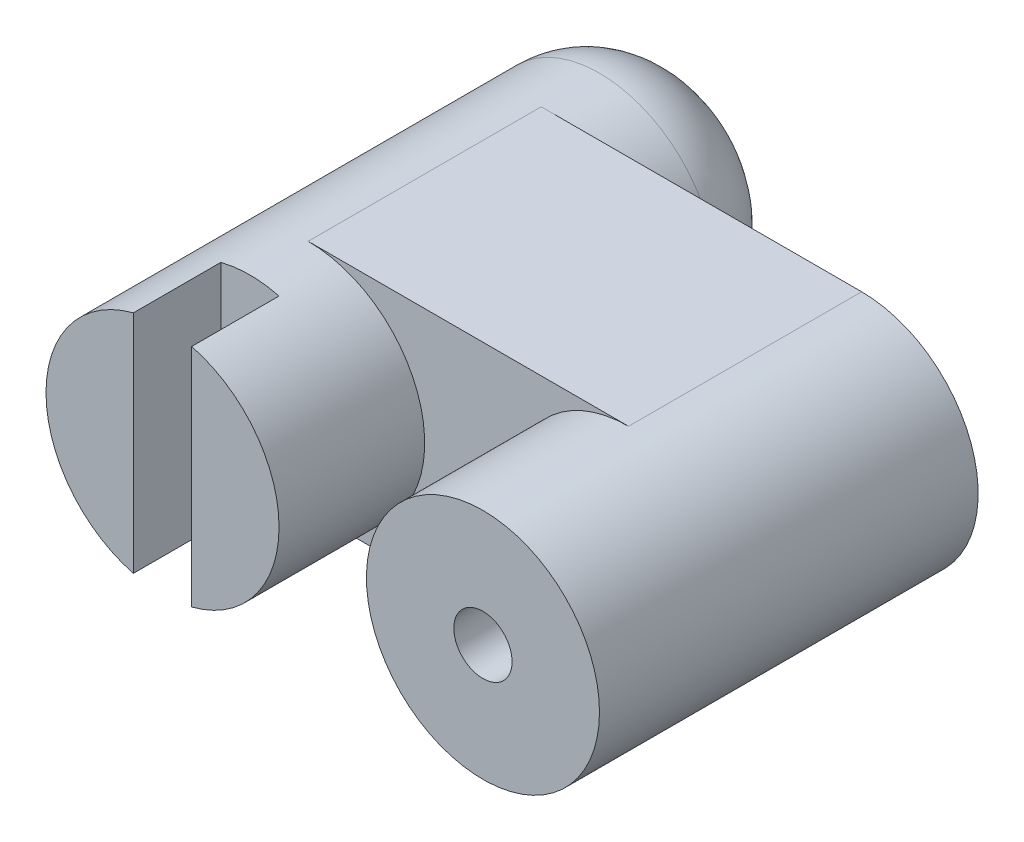
SolidWorks part; units mm, degrees
ref_plane "前视基准面" through (0, 0, 0) normal (0, 0, 1) x (1, 0, 0)
ref_plane "上视基准面" through (0, 0, 0) normal (0, 1, 0) x (1, 0, 0)
ref_plane "右视基准面" through (0, 0, 0) normal (1, 0, 0) x (0, 0, -1)
other "Configuration Table"
sketch "草图1" plane through (0, 0, 0) normal (0, 0, 1) x (1, 0, 0)
  circle A0 centre (0, 0) radius 2
  circle A1 centre (0, 0) radius 0.5
  dimension "D1" = 4
  dimension "D2" = 1
extrude "凸台-拉伸1" add sketch "草图1" along normal blind 9
sketch "草图2" plane through (0, 0, 9) normal (0, 0, 1) x (1, 0, 0)
  line L1 (-0.5, -2.0824) -> (0.5, -2.0824)
  line L2 (-0.5, -2.0824) -> (-0.5, 2.0824)
  line L3 (-0.5, 2.0824) -> (0.5, 2.0824)
  line L4 (0.5, -2.0824) -> (0.5, 2.0824)
  line L5 (-0.5, -2.0824) -> (0.5, 2.0824) construction
  line L6 (-0.5, 2.0824) -> (0.5, -2.0824) construction
  point P0 (0, 0)
  dimension "D1" = 1
extrude "切除-拉伸1" cut sketch "草图2" against normal blind 1.5
fillet "圆角2" radius 1.5 1 edges at (2, 0, 0)
sketch "草图3" plane through (0, 0, 0) normal (0, 1, 0) x (1, 0, 0)
  line L0 (0, 0) -> (0, -2.5) construction
  line L1 (0, -2.5) -> (0, -6.5)
  line L2 (0, -2.5) -> (5.5, -2.5)
  line L3 (5.5, -2.5) -> (5.5, -6.5)
  line L4 (0, -6.5) -> (5.5, -6.5)
  dimension "D1" = 2.5
  dimension "D2" = 4
  dimension "D3" = 5.5
  dimension "D4" = 4
extrude "凸台-拉伸2" add sketch "草图3" along normal mid plane 4
sketch "草图4" plane through (0, 0, 2.5) normal (0, 0, -1) x (-1, 0, 0)
  line L0 (-5.5, 2) -> (-5.5, -2) construction
  circle A0 centre (-5.5, 0) radius 2
  circle A1 centre (-5.5, 0) radius 0.5
  dimension "D1" = 1
extrude "凸台-拉伸3" add sketch "草图4" against normal blind 4
sketch "草图5" plane through (0, 0, 2.5) normal (0, 0, -1) x (-1, 0, 0)
  line L0 (-5.5, 0.5) -> (-5.5, -0.5) construction
  circle A0 centre (-5.5, 0) radius 0.5
  dimension "D1" = 1
extrude "切除-拉伸2" cut sketch "草图5" against normal blind 4
sketch "草图6" plane through (0, 0, 9) normal (0, 0, 1) x (1, 0, 0)
  circle A0 centre (0, 0) radius 0.5
  dimension "D1" = 1
extrude "切除-拉伸3" cut sketch "草图6" against normal through all
sketch "草图7" plane through (0, 0, 6.5) normal (0, 0, 1) x (1, 0, 0)
  circle A0 centre (5.5, 0) radius 2
  circle A1 centre (5.5, 0) radius 0.5
extrude "凸台-拉伸4" add sketch "草图7" along normal blind 2.5
